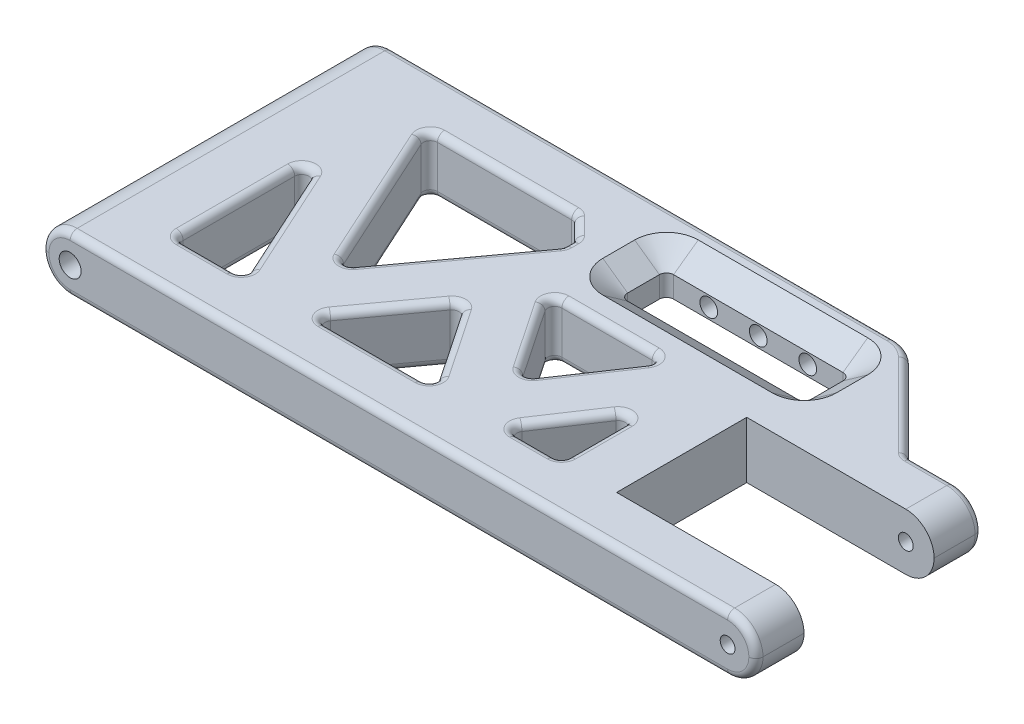
SolidWorks part; units mm, degrees
ref_plane "Plan de face" through (0, 0, 0) normal (0, 0, 1) x (1, 0, 0)
ref_plane "Plan de dessus" through (0, 0, 0) normal (0, 1, 0) x (1, 0, 0)
ref_plane "Plan de droite" through (0, 0, 0) normal (1, 0, 0) x (0, 0, -1)
sketch "Esquisse1" plane through (0, 0, 0) normal (0, 1, 0) x (1, 0, 0)
  line L0 (101, 2.45) -> (101, 9.25)
  line L1 (101, -22.75) -> (0, -22.75)
  line L3 (0, 22.75) -> (0, -22.75)
  line L5 (75, 22.75) -> (0, 22.75)
  line L6 (90.2678, 9.5533) -> (78.5355, 21.2855)
  line L7 (101, 9.25) -> (91, 9.25)
  line L9 (101, -22.75) -> (101, -15.95)
  line L11 (101, -15.95) -> (74.5, -15.95)
  line L12 (74.5, -15.95) -> (74.5, 2.45)
  line L13 (74.5, 2.45) -> (101, 2.45)
  line L14 (66.5, -14.75) -> (66.5, -6.7639)
  line L15 (60.1759, -15.75) -> (65.5, -15.75)
  line L16 (64.6679, -6.2092) -> (59.3439, -14.1953)
  line L17 (46.2259, 2.1909) -> (52.6471, -7.331)
  line L18 (54.3055, -7.3306) -> (60.6829, 2.1359)
  line L19 (59.8241, 3.75) -> (47.055, 3.75)
  line L20 (33.0634, -15.75) -> (46.795, -15.75)
  line L21 (39.3844, -4.371) -> (32.2551, -14.1613)
  line L22 (47.6241, -14.1909) -> (41.0219, -4.4006)
  line L23 (13, -15.75) -> (20.1973, -15.75)
  line L24 (12, 1.0179) -> (12, -14.75)
  line L25 (21.107, -14.3348) -> (13.9097, 1.4332)
  line L26 (17.043, 13.8348) -> (26.2356, -6.3046)
  line L27 (36.9358, 15.25) -> (17.9527, 15.25)
  line L28 (40.0571, 12.5429) -> (37.6429, 14.9571)
  line L29 (40.35, 10.8706) -> (40.35, 11.8358)
  line L30 (27.9537, -6.478) -> (40.1584, 10.2819)
  line L33 (48.35, 16.25) -> (48.35, 11.75)
  line L36 (73.3145, 17.25) -> (49.35, 17.25)
  line L39 (74.35, 11.7855) -> (74.35, 16.2145)
  line L42 (49.35, 10.75) -> (73.3145, 10.75)
  arc A3 (78.5355, 21.2855) -> (75, 22.75) centre (75, 17.75) ccw
  arc A4 (90.2678, 9.5533) -> (91, 9.25) centre (91, 10.2855) ccw
  arc A6 (65.5, -15.75) -> (66.5, -14.75) centre (65.5, -14.75) ccw
  arc A7 (59.3439, -14.1953) -> (60.1759, -15.75) centre (60.1759, -14.75) ccw
  arc A8 (66.5, -6.7639) -> (64.6679, -6.2092) centre (65.5, -6.7639) ccw
  arc A9 (52.6471, -7.331) -> (54.3055, -7.3306) centre (53.4762, -6.7719) ccw
  arc A10 (60.6829, 2.1359) -> (59.8241, 3.75) centre (59.8241, 2.7145) ccw
  arc A11 (47.055, 3.75) -> (46.2259, 2.1909) centre (47.055, 2.75) ccw
  arc A12 (46.795, -15.75) -> (47.6241, -14.1909) centre (46.795, -14.75) ccw
  arc A13 (32.2551, -14.1613) -> (33.0634, -15.75) centre (33.0634, -14.75) ccw
  arc A14 (41.0219, -4.4006) -> (39.3844, -4.371) centre (40.1928, -4.9597) ccw
  arc A15 (20.1973, -15.75) -> (21.107, -14.3348) centre (20.1973, -14.75) ccw
  arc A16 (12, -14.75) -> (13, -15.75) centre (13, -14.75) ccw
  arc A17 (13.9097, 1.4332) -> (12, 1.0179) centre (13, 1.0179) ccw
  arc A18 (26.2356, -6.3046) -> (27.9537, -6.478) centre (27.1453, -5.8894) ccw
  arc A19 (17.9527, 15.25) -> (17.043, 13.8348) centre (17.9527, 14.25) ccw
  arc A20 (37.6429, 14.9571) -> (36.9358, 15.25) centre (36.9358, 14.25) ccw
  arc A21 (40.35, 11.8358) -> (40.0571, 12.5429) centre (39.35, 11.8358) ccw
  arc A22 (40.1584, 10.2819) -> (40.35, 10.8706) centre (39.35, 10.8706) ccw
  arc A23 (48.35, 11.75) -> (49.35, 10.75) centre (49.35, 11.75) ccw
  arc A24 (49.35, 17.25) -> (48.35, 16.25) centre (49.35, 16.25) ccw
  arc A25 (74.35, 16.2145) -> (73.3145, 17.25) centre (73.3145, 16.2145) ccw
  arc A26 (73.3145, 10.75) -> (74.35, 11.7855) centre (73.3145, 11.7855) ccw
  point P3 (0, 0)
  dimension "D1" = 1
  dimension "D2" = 5
  dimension "D3" = 45.5
  dimension "D4" = 101
  dimension "D5" = 32
  dimension "D6" = 6.8
  dimension "D7" = 26.5
  dimension "D8" = 45
  dimension "D9" = 16
  dimension "D10" = 10
  dimension "D11" = 26
  dimension "D12" = 6.5
  dimension "D13" = 5.5
  dimension "D14" = 26.65
extrude "Boss.-Extru.1" add sketch "Esquisse1" along normal blind 4 and the other way blind 4
fillet "Congé2" radius 4 6 edges at (0, 4, 0) (0, -4, 0) (101, 4, 19.35) (101, -4, 19.35) (101, 4, -5.85) (101, -4, -5.85)
fillet "Congé3" radius 1 88 edges at (47.6779, -4, 15.2195) (39.9292, -4, 15.75) (32.1722, -4, 15.2035) (35.8197, -4, 9.2662) (40.2108, -4, 3.9599) (66.2071, 4, 15.4571) (62.838, 4, 15.75) (59.2942, 4, 15.2219) (62.0059, 4, 10.2022) (65.7898, 4, 5.8068) (46.1721, 4, -3.2195) (53.4396, 4, -3.75) (60.7383, 4, -3.2009) (57.4942, 4, 2.5973) (53.4764, 4, 7.7719) (12.7875, 4, -1.9951) (17.5084, 4, 6.4508) (21.0385, 4, 15.2907) (16.5987, 4, 15.75) (12.2929, 4, 15.4571) (17.1115, 4, -14.7907) (27.4442, 4, -15.25) (37.3185, 4, -15.1739) (38.85, 4, -13.75) (40.2739, 4, -12.2185) (40.35, 4, -11.3532) (40.3009, 4, -10.561) (34.056, 4, -1.9019) (27.0449, 4, 6.8843) (1.1716, 2.8284, 22.75) (50.5, 4, 22.75) (99.8284, 2.8284, 22.75) (99.8284, -2.8284, 22.75) (50.5, -4, 22.75) (39.5, -4, -22.75) (76.9134, -4, -22.3694) (84.4017, -4, -15.4194) (90.6037, -4, -9.3288) (94, -4, -9.25) (99.8284, -2.8284, -9.25) (99.8284, 2.8284, -9.25) (94, 4, -9.25) (90.6037, 4, -9.3288) (84.4017, 4, -15.4194) (76.9134, 4, -22.3694) (39.5, 4, -22.75) (1.1716, 2.8284, -22.75) (65.7898, -4, 5.8068) (66.5, -4, 10.7569) (66.2071, -4, 15.4571) (62.838, -4, 15.75) (59.2942, -4, 15.2219) (46.1721, -4, -3.2195) (53.4396, -4, -3.75) (60.7383, -4, -3.2009) (57.4942, -4, 2.5973) (53.4764, -4, 7.7719) (40.2108, 4, 3.9599) (44.323, 4, 9.2957) (47.6779, 4, 15.2195) (39.9292, 4, 15.75) (32.1722, 4, 15.2035) (17.1115, -4, -14.7907) (27.4442, -4, -15.25) (37.3185, -4, -15.1739) (38.85, -4, -13.75) (40.2739, -4, -12.2185) (40.35, -4, -11.3532) (40.3009, -4, -10.561) (34.056, -4, -1.9019) (27.0449, -4, 6.8843) (12.7875, -4, -1.9951) (17.5084, -4, 6.4508) (21.0385, -4, 15.2907) (16.5987, -4, 15.75) (12.2929, -4, 15.4571) (44.323, -4, 9.2957) (66.5, 4, 10.7569) (49.4365, 4, 2.57) (12, 4, 6.866) (21.6393, 4, -3.7651) (1.1716, -2.8284, 22.75) (1.1716, -2.8284, -22.75) (62.0059, -4, 10.2022) (49.4365, -4, 2.57) (35.8197, 4, 9.2662) (21.6393, -4, -3.7651) (12, -4, 6.866)
chamfer "Chanfrein1" distance 2.5 distance2 3.5 8 edges at (61.3322, -4, -17.25) (48.6429, -4, -16.9571) (74.0467, -4, -16.9467) (48.35, -4, -14) (74.35, -4, -14) (48.6429, -4, -11.0429) (74.0467, -4, -11.0533) (61.3322, -4, -10.75) first distance on face at (61.3322, 0, -17.25) first distance on face at (48.7464, 0, -16.8536) first distance on face at (73.9395, 0, -16.8395) first distance on face at (48.35, 0, -14) first distance on face at (74.35, 0, -14) first distance on face at (48.7464, 0, -11.1464) first distance on face at (73.9395, 0, -11.1605) first distance on face at (61.3322, 0, -10.75)
sketch "Esquisse2" plane through (0, 0, 22.75) normal (0, 0, 1) x (1, 0, 0)
  circle A0 centre (4, 0) radius 1.55
  circle A1 centre (97, 0) radius 1.05
  dimension "D1" = 3.1
  dimension "D2" = 2.1
extrude "Enlèv. mat.-Extru.1" cut sketch "Esquisse2" against normal through all
chamfer "Chanfrein2" distance 3.5 distance2 2.5 8 edges at (61.3322, 4, -17.25) (48.6429, 4, -16.9571) (74.0467, 4, -16.9467) (48.35, 4, -14) (74.35, 4, -14) (48.6429, 4, -11.0429) (74.0467, 4, -11.0533) (61.3322, 4, -10.75) first distance on face at (63.8197, 4, 12.3104)
hole_wizard "Trou taraudé M31" positions "Esquisse5" profile "Esquisse4" tap size "M3" standard "ISO"
sketch "Esquisse5" plane through (0, 0, -22.75) normal (0, 0, -1) x (-1, 0, 0)
  line L0 (-73.3145, -1.5) -> (-49.35, -1.5) construction
  point P0 (-61.3322, 0)
  point P1 (-54.3322, 0)
  point P3 (-68.3322, 0)
  point P6 (-61.3322, -1.5)
  dimension "D1" = 7
  dimension "D2" = 7
sketch "Esquisse4" plane through (61.3322, 0, -22.75) normal (1, 0, 0) x (0, 1, 0)
  line L0 (0, 0) -> (0, 16.7511)
  line L1 (0, 16.7511) -> (1.25, 16)
  line L2 (1.25, 16) -> (1.25, 0)
  line L5 (1.25, 0) -> (0, 0)
  line L10 (0, 16.7511) -> (-1.25, 16) construction
  line L11 (0, -6.35) -> (0, 107.95) construction
  dimension "Diamètre du trou pour taraudage" = 2.5
  dimension "Profondeur du trou pour taraudage" = 16
  dimension "Angle de pointe" = 118
cosmetic thread "Filetage de perçage1" parameters "D1"=16, "D2"=3
cosmetic thread "Filetage de perçage3" parameters "D1"=16, "D2"=3
cosmetic thread "Filetage de perçage4" parameters "D1"=16, "D2"=3
